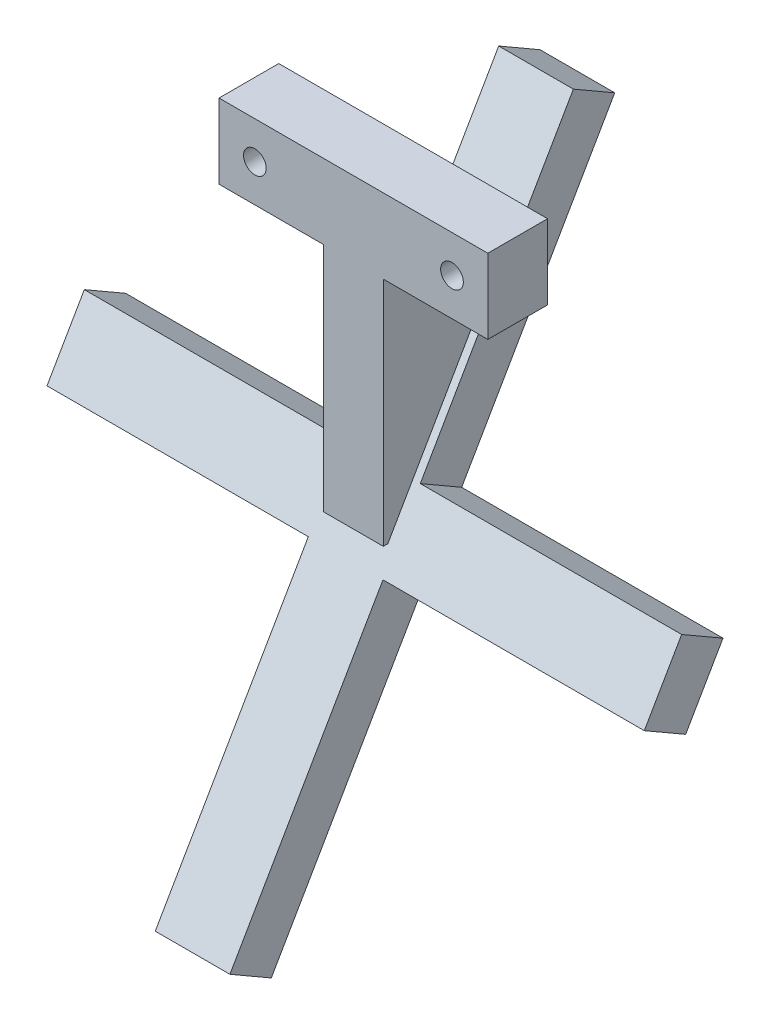
SolidWorks part; units mm, degrees
ref_plane "Front Plane" through (0, 0, 0) normal (0, 0, 1) x (1, 0, 0)
ref_plane "Top Plane" through (0, 0, 0) normal (0, 1, 0) x (1, 0, 0)
ref_plane "Right Plane" through (0, 0, 0) normal (1, 0, 0) x (0, 0, -1)
sketch "Sketch1" plane through (0, 0, 0) normal (1, 0, 0) x (0, 0, -1)
  line L0 (7.5, 0) -> (17.5, 0) construction
  line L1 (7.5, -23.15) -> (7.5, 23.15) construction
  line L2 (17.5, -6.25) -> (17.5, 6.25)
  line L3 (17.5, 6.25) -> (7.5, 6.25)
  line L4 (7.5, 6.25) -> (7.5, -6.25)
  line L5 (17.5, -6.25) -> (7.5, -6.25)
  dimension "D1" = 10
  dimension "D2" = 12.5
extrude "Boss-Extrude1" add sketch "Sketch1" along normal blind 22.5 and the other way blind 22.5
sketch "Sketch2" plane through (0, 0, 0) normal (1, 0, 0) x (0, 0, -1)
  line L0 (17.5, -6.25) -> (17.5, -45)
  line L1 (7.5, -6.25) -> (7.5, -45)
  line L2 (7.5, -45) -> (17.5, -45)
  line L3 (17.5, -6.25) -> (7.5, -6.25)
  line L4 (12.5, -45) -> (12.5, 0) construction
  line L5 (7.5, 0) -> (17.5, 0) construction
  dimension "D1" = 45
extrude "Boss-Extrude2" add sketch "Sketch2" along normal blind 5 and the other way blind 5
hole_wizard "#6 Clearance Hole1" positions "Sketch5" profile "Sketch6" hole size "#6" standard "ANSI Inch" end condition through all
sketch "Sketch5" plane through (0, 0, -17.5) normal (0, 0, -1) x (-1, 0, 0)
  point P0 (16.5, 0)
  point P3 (-16.5, 0)
sketch "Sketch6" plane through (-16.5, 0, -17.5) normal (1, 0, 0) x (0, 1, 0)
  line L0 (0, 0) -> (0, 10)
  line L1 (0, 10) -> (1.8986, 10)
  line L2 (1.8986, 10) -> (1.8986, 0)
  line L5 (1.8986, 0) -> (0, 0)
  line L11 (0, -6.35) -> (0, 107.95) construction
  dimension "Thru Hole Dia." = 3.7973
  dimension "Thru Hole Depth" = 10
ref_plane "Plane1" through (0, -18.8277, -32.6106) normal (0, -0.5, -0.866) x (1, 0, 0)
sketch "Sketch3" plane through (0, 4.2901, -45.9577) normal (0, 0.5, 0.866) x (-1, 0, 0)
  line L0 (-5, 59.4153) -> (5, 59.4153) construction
  line L1 (-5, 61.9153) -> (-5, 56.9153) construction
  line L2 (5, 61.9153) -> (5, 56.9153) construction
  line L3 (0, 61.9153) -> (0, 56.9153) construction
  line L4 (5, 61.9153) -> (-5, 61.9153) construction
  line L5 (5, 56.9153) -> (-5, 56.9153) construction
  line L6 (0, 61.9153) -> (0, 116.9153) construction
  line L7 (-5, 59.4153) -> (50, 59.4153) construction
  line L8 (50, 53.1653) -> (50, 65.6653)
  line L9 (50, 65.6653) -> (6.25, 65.6653)
  line L10 (6.25, 65.6653) -> (6.25, 116.9153)
  line L11 (6.25, 116.9153) -> (-6.25, 116.9153)
  line L12 (0, 59.4153) -> (6.25, 65.6653) construction
  line L13 (50, 53.1653) -> (6.25, 53.1653)
  line L14 (6.25, 53.1653) -> (6.25, 1.9153)
  line L15 (6.25, 1.9153) -> (-6.25, 1.9153)
  line L16 (-6.25, 53.1653) -> (-6.25, 1.9153)
  line L17 (-50, 53.1653) -> (-50, 65.6653)
  line L18 (-50, 53.1653) -> (-6.25, 53.1653)
  line L19 (-50, 65.6653) -> (-6.25, 65.6653)
  line L20 (-6.25, 65.6653) -> (-6.25, 116.9153)
  point P25 (0, 1.9153)
  dimension "D1" = 45
  dimension "D2" = 12.5
  dimension "D3" = 50
extrude "Boss-Extrude5" add sketch "Sketch3" along normal blind 8
fillet "Fillet2" radius 5 1 edges at (0, -29, -17.5)
